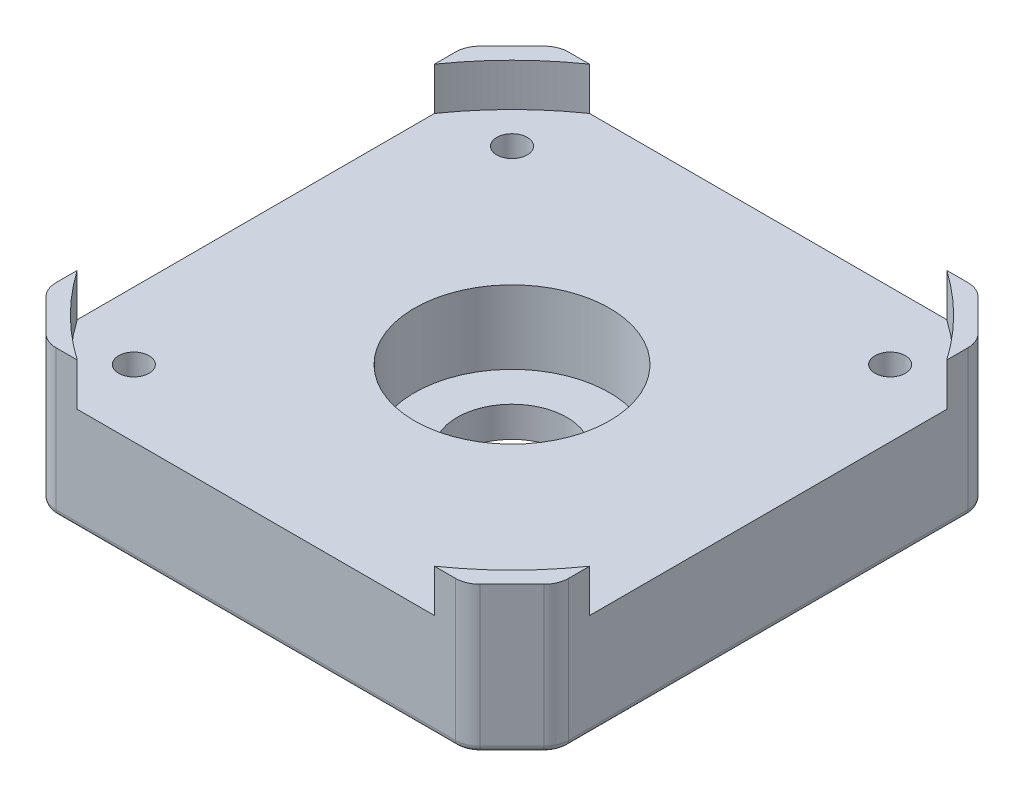
SolidWorks part; units mm, degrees
ref_plane "Спереди" through (0, 0, 0) normal (0, 0, 1) x (1, 0, 0)
ref_plane "Сверху" through (0, 0, 0) normal (0, 1, 0) x (1, 0, 0)
ref_plane "Справа" through (0, 0, 0) normal (1, 0, 0) x (0, 0, -1)
sketch "Эскиз1" plane through (0, 0, 0) normal (0, 1, 0) x (1, 0, 0)
  line L0 (-21, 17.2) -> (-17.2, 21)
  line L1 (-17.2, -21) -> (17.2, -21)
  line L2 (-21, -17.2) -> (-21, 17.2)
  line L3 (-17.2, 21) -> (17.2, 21)
  line L4 (21, -17.2) -> (21, 17.2)
  line L5 (-21, -21) -> (21, 21) construction
  line L6 (-21, 21) -> (21, -21) construction
  line L7 (17.2, 21) -> (21, 17.2)
  line L8 (17.2, -21) -> (21, -17.2)
  line L9 (-21, -17.2) -> (-17.2, -21)
  line L11 (-15.5, -15.5) -> (15.5, -15.5) construction
  line L12 (-15.5, -15.5) -> (-15.5, 15.5) construction
  line L13 (-15.5, 15.5) -> (15.5, 15.5) construction
  line L14 (15.5, -15.5) -> (15.5, 15.5) construction
  line L15 (-15.5, -15.5) -> (15.5, 15.5) construction
  line L16 (-15.5, 15.5) -> (15.5, -15.5) construction
  circle A0 centre (-15.5, 15.5) radius 1.25
  circle A1 centre (15.5, 15.5) radius 1.25
  circle A2 centre (15.5, -15.5) radius 1.25
  circle A3 centre (-15.5, -15.5) radius 1.25
  circle A4 centre (0, 0) radius 4.5
  circle A5 centre (0, 0) radius 16.5
  circle A6 centre (0, 0) radius 11
  arc A7 (-21, -14.641) -> (-14.641, -21) centre (0, 0) ccw
  arc A8 (-14.641, 21) -> (-21, 14.641) centre (0, 0) ccw
  arc A9 (21, 14.641) -> (14.641, 21) centre (0, 0) ccw
  arc A10 (14.641, -21) -> (21, -14.641) centre (0, 0) ccw
  circle A11 centre (-15.5, 15.5) radius 2.65
  circle A12 centre (15.5, 15.5) radius 2.65
  circle A13 centre (15.5, -15.5) radius 2.65
  circle A14 centre (-15.5, -15.5) radius 2.65
  point P0 (0, 0)
  point P14 (0, 0)
  dimension "D1" = 2.5
  dimension "D2" = 5.3
  dimension "D3" = 9
  dimension "D8" = 22
  dimension "D9" = 33
  dimension "D10" = 25.6
  dimension "D11" = 31
  dimension "D12" = 34.4
extrude "Бобышка-Вытянуть1" add sketch "Эскиз1" along normal blind 8.5 contours L1 A10 L4 A9 L3 A8 L2 A7 A5 A3 A2 A1 A0 | A5 A6 | A6 A4 | A14 A3 | A13 A2 | A11 A0 | A12 A1 region at (-17.6819, 0, -17.6819) region at (-16.0333, 0, 0) region at (-10.6889, 0, 0) region at (-18.075, 0, -15.5) region at (12.925, 0, -15.5) region at (12.925, 0, 15.5) region at (-18.075, 0, 15.5)
extrude "Бобышка-Вытянуть2" add sketch "Эскиз1<4>" along normal blind 12 contours A10 L1 L8 L4 | A7 L2 L9 L1 | A8 L3 L0 L2 | A9 L4 L7 L3 region at (-18.5132, 0, -18.5132) region at (-18.5132, 0, 18.5132) region at (18.5132, 0, -18.5132) region at (18.5132, 0, 18.5132)
sketch "Эскиз1<4>" plane through (0, 0, 0) normal (0, 1, 0) x (1, 0, 0) same geometry as "Эскиз1"
chamfer "Фаска1" distance 2.5 angle 45 4 edges at (-15.5, 0, -14.25) (15.5, 0, -14.25) (15.5, 0, 16.75) (-15.5, 0, 16.75)
sketch "Эскиз2" plane through (0, 8.5, 0) normal (0, 1, 0) x (1, 0, 0)
  circle A0 centre (0, 0) radius 8
extrude "Вырез-Вытянуть1" cut sketch "Эскиз2" against normal blind 6
fillet "Скругление1" radius 2 8 edges at (21, 6, 17.2) (17.2, 6, 21) (-17.2, 6, 21) (-21, 6, 17.2) (-21, 6, -17.2) (-17.2, 6, -21) (17.2, 6, -21) (21, 6, -17.2)
fillet "Скругление2" radius 0.5 16 edges at (-17.1369, 0, 20.8478) (-19.1, 0, 19.1) (-20.8478, 0, 17.1369) (-21, 0, 0) (-20.8478, 0, -17.1369) (-19.1, 0, -19.1) (-17.1369, 0, -20.8478) (0, 0, -21) (17.1369, 0, -20.8478) (19.1, 0, -19.1) (20.8478, 0, -17.1369) (21, 0, 0) (20.8478, 0, 17.1369) (19.1, 0, 19.1) (17.1369, 0, 20.8478) (0, 0, 21)
sketch "Эскиз3" plane through (0, 0, 21) normal (0, 0, 1) x (1, 0, 0)
  line L0 (-14.641, 8.5) -> (14.641, 8.5) construction
  line L1 (-4, 1.3085) -> (4, 1.3085)
  line L2 (-4, 1.3085) -> (-4, 8.5)
  line L3 (-4, 8.5) -> (4, 8.5)
  line L4 (4, 1.3085) -> (4, 8.5)
  line L5 (-4, 1.3085) -> (4, 8.5) construction
  line L6 (-4, 8.5) -> (4, 1.3085) construction
  line L8 (3.0759, 2.1393) -> (-3.0759, 2.1393)
  line L9 (3.0759, 2.1393) -> (3.0759, 7.6693)
  line L10 (3.0759, 7.6693) -> (-3.0759, 7.6693)
  line L11 (-3.0759, 2.1393) -> (-3.0759, 7.6693)
  line L12 (3.0759, 2.1393) -> (-3.0759, 7.6693) construction
  line L13 (3.0759, 7.6693) -> (-3.0759, 2.1393) construction
  point P0 (0, 4.9043)
  point P7 (0, 4.9043)
extrude "Бобышка-Вытянуть3" [suppressed] add sketch "Эскиз3" along normal blind 0.5
